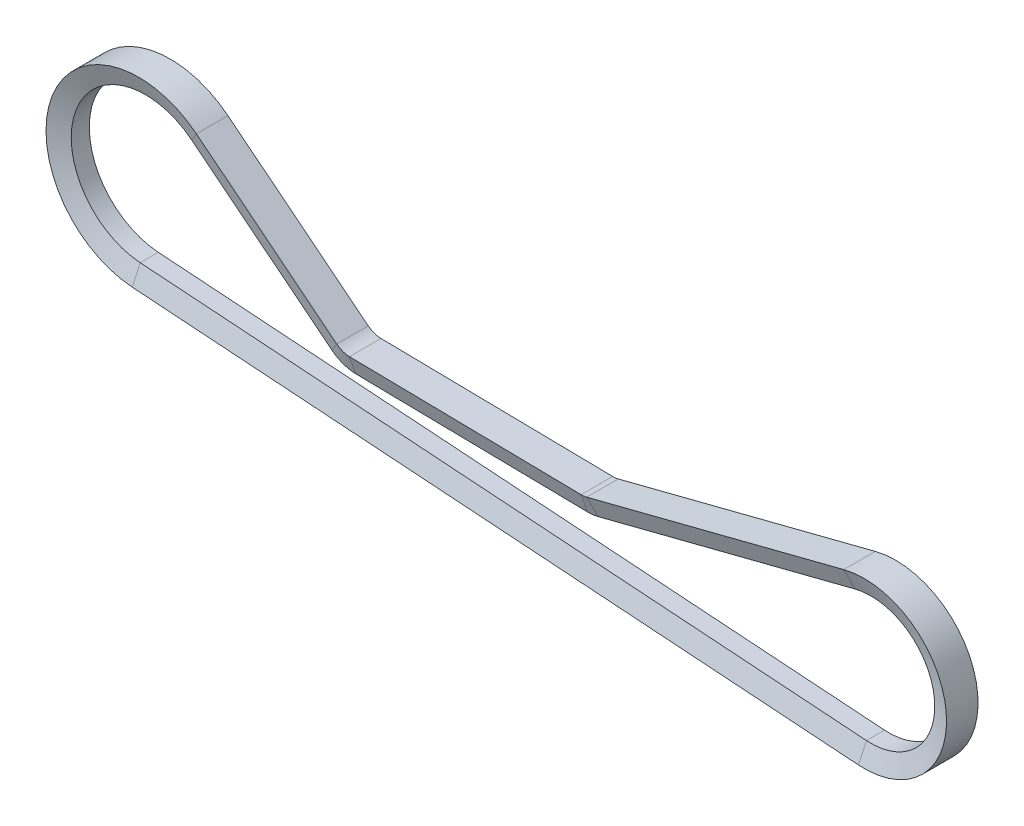
SolidWorks part; units mm, degrees
ref_plane "Front Plane" through (0, 0, 0) normal (0, 0, 1) x (1, 0, 0)
ref_plane "Top Plane" through (0, 0, 0) normal (0, 1, 0) x (1, 0, 0)
ref_plane "Right Plane" through (0, 0, 0) normal (1, 0, 0) x (0, 0, -1)
sketch "Sketch2" plane through (0, 0, 0) normal (0, 0, 1) x (1, 0, 0)
  line L0 (0, 0) -> (1, 0) construction
  line L1 (0, 0) -> (0, 1) construction
  line L12 (-1.7321, -24.8146) -> (-221.176, -9.4967)
  line L14 (-201.7705, 40.3282) -> (-159.3811, 6.53)
  line L15 (-155.5243, 5.1458) -> (-85.5333, 4.0228)
  line L16 (-83.8574, 4.2201) -> (-6.166, 24.0987)
  arc A4 (-221.176, -9.4967) -> (-201.7705, 40.3282) centre (-219.2262, 18.4353) cw
  arc A7 (-6.166, 24.0987) -> (-1.7321, -24.8146) centre (0, 0) cw
  arc A8 (-159.3811, 6.53) -> (-155.5243, 5.1458) centre (-155.4224, 11.495) ccw
  arc A9 (-85.5333, 4.0228) -> (-83.8574, 4.2201) centre (-85.4314, 10.372) ccw
ref_plane "Plane4" through (-6.166, 24.0987, 0) normal (0.9688, 0.2479, 0) x (0.2479, -0.9688, 0)
sketch "Sketch3" plane through (-6.166, 24.0987, 0) normal (0.9688, 0.2479, 0) x (0.2479, -0.9688, 0)
  line L0 (0, -4.7625) -> (0, 4.7625)
  line L1 (0, -4.7625) -> (5.588, -2.7286)
  line L2 (5.588, -2.7286) -> (5.588, 2.7286)
  line L3 (5.588, 2.7286) -> (0, 4.7625)
  line L4 (0, 0) -> (5.588, 0) construction
  dimension "D1" = 9.525
  dimension "D2" = 5.588
  dimension "D3" = 40
sweep "Sweep1" add profiles "Sketch3" path "Sketch2"
